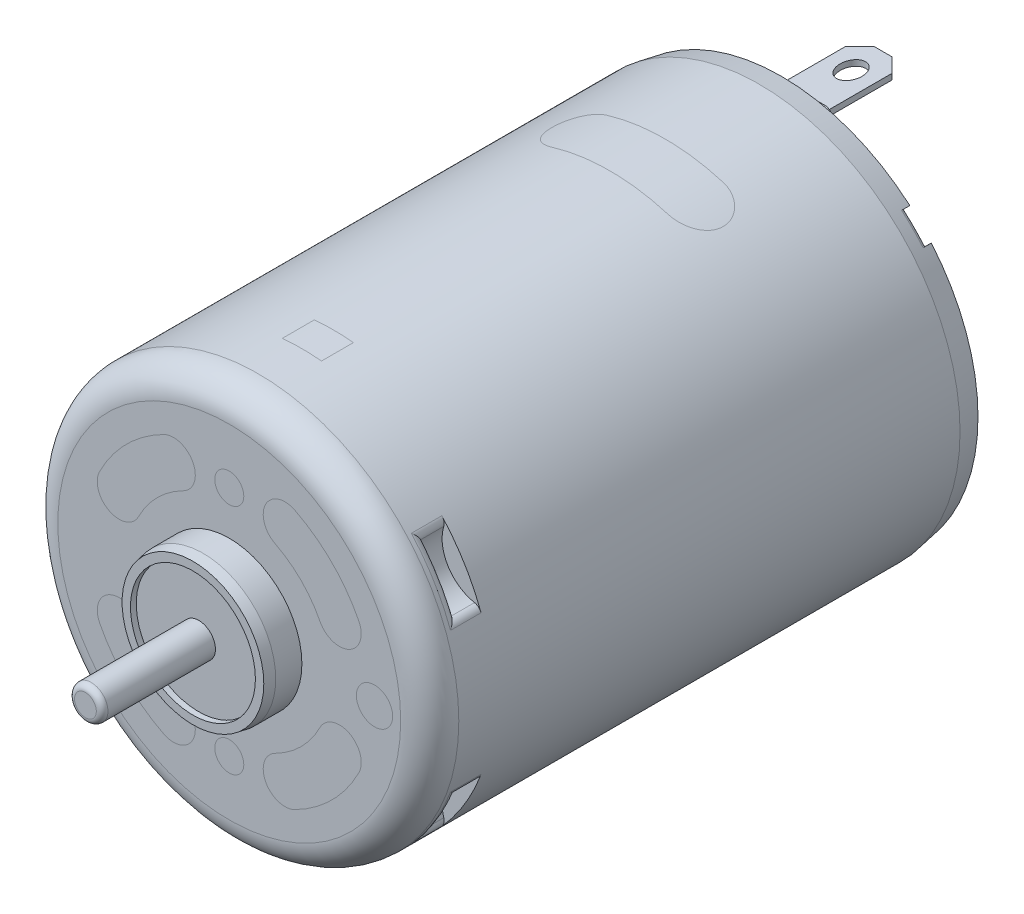
SolidWorks part; units mm, degrees
ref_plane "正面" through (0, 0, 0) normal (0, 0, 1) x (1, 0, 0)
ref_plane "平面" through (0, 0, 0) normal (0, 1, 0) x (1, 0, 0)
ref_plane "右側面" through (0, 0, 0) normal (1, 0, 0) x (0, 0, -1)
sketch "ｽｹｯﾁ1" plane through (0, 0, 0) normal (0, 0, 1) x (1, 0, 0)
  circle A0 centre (0, 0) radius 13.8
  dimension "D1" = 27.6
extrude "ﾎﾞｽ - 押し出し1" add sketch "ｽｹｯﾁ1" along normal blind 38
sketch "ｽｹｯﾁ2" plane through (0, 0, 0) normal (0, 0, -1) x (-1, 0, 0)
  circle A0 centre (0, 0) radius 9.6
  dimension "D1" = 19.2
extrude "ﾎﾞｽ - 押し出し2" add sketch "ｽｹｯﾁ2" along normal blind 0.3
sketch "ｽｹｯﾁ3" plane through (0, 0, 0) normal (0, 0, -1) x (-1, 0, 0)
  circle A0 centre (0, 0) radius 9.6 construction
  circle A1 centre (0, 0) radius 9.6
  circle A4 centre (0, 0) radius 13.2
  circle A5 centre (0, 0) radius 13.2
  dimension "D1" = 0.6
extrude "ｶｯﾄ - 押し出し1" cut sketch "ｽｹｯﾁ3" against normal blind 0.5
fillet "ﾌｨﾚｯﾄ1" radius 0.8 1 edges at (-9.6, 0, -0.3)
fillet "ﾌｨﾚｯﾄ2" radius 2 1 edges at (13.8, 0, 38)
sketch "ｽｹｯﾁ4" plane through (0, 0, 38) normal (0, 0, 1) x (1, 0, 0)
  circle A0 centre (0, 0) radius 5
  dimension "D1" = 10
extrude "ﾎﾞｽ - 押し出し3" add sketch "ｽｹｯﾁ4" along normal blind 2.5
sketch "ｽｹｯﾁ5" plane through (0, 0, 40.5) normal (0, 0, 1) x (1, 0, 0)
  circle A0 centre (0, 0) radius 1.15
  dimension "D1" = 2.3
extrude "ﾎﾞｽ - 押し出し4" add sketch "ｽｹｯﾁ5" along normal blind 7.4
fillet "ﾌｨﾚｯﾄ3" radius 0.4 1 edges at (1.15, 0, 47.9)
sketch "ｽｹｯﾁ6" plane through (0, 0, 40.5) normal (0, 0, 1) x (1, 0, 0)
  circle A0 centre (0, 0) radius 4.3
  circle A2 centre (0, 0) radius 1.15 construction
  circle A3 centre (0, 0) radius 1.15
  dimension "D1" = 8.6
extrude "ｶｯﾄ - 押し出し5" cut sketch "ｽｹｯﾁ6" against normal blind 0.4
chamfer "面取り1" distance 0.7 angle 10 1 edges at (5, 0, 40.5) first distance on face at (5, 0, 40.5)
chamfer "面取り2" distance 1.5 angle 10 1 edges at (13.8, 0, 0) first distance on face at (13.8, 0, 36)
sketch "ｽｹｯﾁ7" plane through (0, 0, -0.3) normal (0, 0, -1) x (-1, 0, 0)
  circle A0 centre (0, 0) radius 4.95
  dimension "D1" = 9.9
extrude "ﾎﾞｽ - 押し出し5" add sketch "ｽｹｯﾁ7" along normal blind 2.7
sketch "ｽｹｯﾁ8" plane through (0, 0, -3) normal (0, 0, -1) x (-1, 0, 0)
  circle A0 centre (0, 0) radius 1.15
  dimension "D1" = 2.3
extrude "ﾎﾞｽ - 押し出し6" add sketch "ｽｹｯﾁ8" along normal blind 0.2
sketch "ｽｹｯﾁ9" plane through (0, 0, -3) normal (0, 0, -1) x (-1, 0, 0)
  circle A1 centre (0, 0) radius 1.15 construction
  circle A2 centre (0, 0) radius 4.35
  circle A3 centre (0, 0) radius 4.35
  circle A4 centre (0, 0) radius 1.15
  dimension "D1" = 0.6
extrude "ｶｯﾄ - 押し出し6" cut sketch "ｽｹｯﾁ9" against normal blind 0.6
fillet "ﾌｨﾚｯﾄ4" radius 0.4 1 edges at (-1.15, 0, -3.2)
sketch "ｽｹｯﾁ10" plane through (0, 0, 38) normal (0, 0, 1) x (1, 0, 0)
  line L0 (-6.0104, 6.0104) -> (0, 0) construction
  line L1 (0, 0) -> (0, 8) construction
  circle A0 centre (0, 8) radius 1
  circle A1 centre (0, -8) radius 1
  circle A2 centre (0, 0) radius 0.75 construction
  arc A3 (-3.837, 7.5847) -> (-7.5847, 3.837) centre (0, 0) ccw construction
  arc A4 (-4.5141, 8.9232) -> (-8.9232, 4.5141) centre (0, 0) ccw
  arc A5 (-3.1599, 6.2462) -> (-6.2462, 3.1599) centre (0, 0) ccw
  arc A6 (-3.1599, 6.2462) -> (-4.5141, 8.9232) centre (-3.837, 7.5847) ccw
  arc A7 (-8.9232, 4.5141) -> (-6.2462, 3.1599) centre (-7.5847, 3.837) ccw
  circle A8 centre (0, 0) radius 5 construction
  arc A9 (7.5847, 3.837) -> (3.837, 7.5847) centre (0, 0) ccw construction
  arc A10 (8.9232, 4.5141) -> (4.5141, 8.9232) centre (0, 0) ccw
  arc A11 (6.2462, 3.1599) -> (3.1599, 6.2462) centre (0, 0) ccw
  arc A12 (6.2462, 3.1599) -> (8.9232, 4.5141) centre (7.5847, 3.837) ccw
  arc A13 (4.5141, 8.9232) -> (3.1599, 6.2462) centre (3.837, 7.5847) ccw
  arc A14 (3.837, -7.5847) -> (7.5847, -3.837) centre (0, 0) ccw construction
  arc A15 (4.5141, -8.9232) -> (8.9232, -4.5141) centre (0, 0) ccw
  arc A16 (3.1599, -6.2462) -> (6.2462, -3.1599) centre (0, 0) ccw
  arc A17 (3.1599, -6.2462) -> (4.5141, -8.9232) centre (3.837, -7.5847) ccw
  arc A18 (8.9232, -4.5141) -> (6.2462, -3.1599) centre (7.5847, -3.837) ccw
  arc A19 (-7.5847, -3.837) -> (-3.837, -7.5847) centre (0, 0) ccw construction
  arc A20 (-8.9232, -4.5141) -> (-4.5141, -8.9232) centre (0, 0) ccw
  arc A21 (-6.2462, -3.1599) -> (-3.1599, -6.2462) centre (0, 0) ccw
  arc A22 (-6.2462, -3.1599) -> (-8.9232, -4.5141) centre (-7.5847, -3.837) ccw
  arc A23 (-4.5141, -8.9232) -> (-3.1599, -6.2462) centre (-3.837, -7.5847) ccw
  circle A24 centre (10, 0) radius 1.25
  circle A25 centre (0, 0) radius 4.3 construction
  point P3 (-6.0104, 6.0104)
  point P6 (0, 0)
  point P24 (6.0104, 6.0104)
  point P31 (6.0104, -6.0104)
  point P38 (-6.0104, -6.0104)
  point P45 (0, 0)
  dimension "D2" = 2
  dimension "D3" = 8
  dimension "D4" = 1.5
  dimension "D6" = 2
  dimension "D9" = 10
  dimension "D10" = 2.5
  dimension "D5" = 5.3
  dimension "D7" = 45
  dimension "D1" = 2
  dimension "D8" = 4
split line "分割ﾗｲﾝ1"
ref_plane "平面1" through (0, 13.8, 0) normal (0, 1, 0) x (1, 0, 0)
sketch "ｽｹｯﾁ11" plane through (0, 13.8, 0) normal (0, 1, 0) x (1, 0, 0)
  line L0 (0, 0) -> (0, -38) construction
  line L2 (-4, -9.9) -> (4, -9.9) construction
  line L3 (-4, -8) -> (4, -8)
  line L4 (-4, -11.8) -> (4, -11.8)
  line L5 (13.5355, 0) -> (-13.5355, 0) construction
  line L6 (-5, -38) -> (5, -38) construction
  arc A0 (-4, -8) -> (-4, -11.8) centre (-4, -9.9) ccw
  arc A1 (4, -11.8) -> (4, -8) centre (4, -9.9) ccw
  point P7 (0, -9.9)
  point P12 (-5.9, -9.9)
  point P13 (5.9, -9.9)
  dimension "D1" = 11.8
  dimension "D2" = 3.8
  dimension "D3" = 8
split line "分割ﾗｲﾝ2"
sketch "ｽｹｯﾁ12" plane through (0, 0, 0) normal (0, 1, 0) x (1, 0, 0)
  line L0 (0, 0) -> (0, -38) construction
  line L1 (-5, -38) -> (5, -38) construction
  line L2 (-4, -11.8) -> (4, -11.8) construction
  line L3 (-1.35, -30.8) -> (1.35, -30.8)
  line L4 (-1.35, -30.8) -> (-1.35, -33)
  line L5 (-1.35, -33) -> (1.35, -33)
  line L6 (1.35, -30.8) -> (1.35, -33)
  line L7 (-1.35, -30.8) -> (1.35, -33) construction
  line L8 (-1.35, -33) -> (1.35, -30.8) construction
  point P5 (0, -31.9)
  dimension "D1" = 2.7
  dimension "D2" = 2.2
  dimension "D3" = 19
split line "分割ﾗｲﾝ3"
sketch "ｽｹｯﾁ13" plane through (0, 0, 0) normal (0, 1, 0) x (1, 0, 0)
  line L0 (0, 0) -> (0, -38) construction
  line L1 (-11.8, -38) -> (11.8, -38) construction
  line L2 (3, -26.5) -> (4.7, -26.5)
  line L3 (5.2, -26) -> (5.2, -21.076)
  line L4 (3, -16.5) -> (3.4319, -16.5)
  line L5 (2.5, -17) -> (2.5, -26)
  line L6 (4.5141, -38) -> (8.9232, -38) construction
  line L7 (3.9093, -16.8515) -> (5.1774, -20.9274)
  line L8 (-3.9093, -16.8515) -> (-5.1774, -20.9274)
  line L9 (-2.5, -17) -> (-2.5, -26)
  line L10 (-3, -16.5) -> (-3.4319, -16.5)
  line L11 (-5.2, -26) -> (-5.2, -21.076)
  line L12 (-3, -26.5) -> (-4.7, -26.5)
  arc A0 (3, -16.5) -> (2.5, -17) centre (3, -17) ccw
  arc A1 (3.4319, -16.5) -> (3.9093, -16.8515) centre (3.4319, -17) cw
  arc A2 (5.2, -21.076) -> (5.1774, -20.9274) centre (4.7, -21.076) ccw
  arc A3 (4.7, -26.5) -> (5.2, -26) centre (4.7, -26) ccw
  arc A4 (3, -26.5) -> (2.5, -26) centre (3, -26) cw
  arc A5 (-3, -26.5) -> (-2.5, -26) centre (-3, -26) ccw
  arc A6 (-4.7, -26.5) -> (-5.2, -26) centre (-4.7, -26) cw
  arc A7 (-5.2, -21.076) -> (-5.1774, -20.9274) centre (-4.7, -21.076) cw
  arc A8 (-3.4319, -16.5) -> (-3.9093, -16.8515) centre (-3.4319, -17) ccw
  arc A9 (-3, -16.5) -> (-2.5, -17) centre (-3, -17) cw
  point P14 (2.5, -16.5)
  point P17 (3.8, -16.5)
  point P20 (5.2, -21)
  point P23 (5.2, -26.5)
  point P26 (2.5, -26.5)
  point P42 (-2.5, -26.5)
  point P43 (-5.2, -26.5)
  point P44 (-5.2, -21)
  point P45 (-3.8, -16.5)
  point P46 (-2.5, -16.5)
  dimension "D7" = 0.5
  dimension "D1" = 10
  dimension "D2" = 2.7
  dimension "D3" = 5.5
  dimension "D4" = 2.5
  dimension "D5" = 11.5
  dimension "D6" = 1.3
split line "分割ﾗｲﾝ4"
sketch "ｽｹｯﾁ14" plane through (0, 0, 0.5) normal (0, 0, -1) x (-1, 0, 0)
  line L0 (2.5, -12.3) -> (2.5, -10.3)
  line L1 (-2.5, 12.3) -> (2.5, 12.3)
  line L2 (-2.5, 12.3) -> (-2.5, 10.3)
  line L3 (-2.5, 10.3) -> (2.5, 10.3)
  line L4 (2.5, 12.3) -> (2.5, 10.3)
  line L5 (-2.5, 12.3) -> (2.5, 10.3) construction
  line L6 (-2.5, 10.3) -> (2.5, 12.3) construction
  line L7 (2.5, -12.3) -> (-2.5, -12.3)
  line L8 (-2.5, -12.3) -> (-2.5, -10.3)
  line L9 (2.5, -10.3) -> (-2.5, -10.3)
  point P0 (0, 11.3)
  point P12 (0, 0)
  dimension "D1" = 2
  dimension "D2" = 5
  dimension "D4" = 24.6
  dimension "D3" = 2
extrude "ﾎﾞｽ - 押し出し7" add sketch "ｽｹｯﾁ14" along normal blind 1.5
fillet "ﾌｨﾚｯﾄ5" radius 0.5 8 edges at (2.5, -12.3, -0.25) (2.5, -10.3, -0.25) (-2.5, -12.3, -0.25) (-2.5, -10.3, -0.25) (2.5, 10.3, -0.25) (2.5, 12.3, -0.25) (-2.5, 10.3, -0.25) (-2.5, 12.3, -0.25)
sketch "ｽｹｯﾁ15" plane through (0, 0, -1) normal (0, 0, -1) x (-1, 0, 0)
  line L0 (2.5, 10.8) -> (2.5, 11.8) construction
  line L1 (-1.6, 11.5) -> (1.6, 11.5)
  line L2 (-1.6, 11.5) -> (-1.6, 11.1)
  line L3 (-1.6, 11.1) -> (1.6, 11.1)
  line L4 (1.6, 11.5) -> (1.6, 11.1)
  line L5 (-1.6, 11.5) -> (1.6, 11.1) construction
  line L6 (-1.6, 11.1) -> (1.6, 11.5) construction
  line L7 (2, 12.3) -> (-2, 12.3) construction
  line L8 (1.6, -11.5) -> (1.6, -11.1)
  line L9 (1.6, -11.5) -> (-1.6, -11.5)
  line L10 (-1.6, -11.5) -> (-1.6, -11.1)
  line L11 (1.6, -11.1) -> (-1.6, -11.1)
  point P0 (0, 11.3)
  point P7 (2.5, 11.3)
  point P10 (0, 12.3)
  point P17 (0, 0)
  dimension "D1" = 0.4
  dimension "D2" = 3.2
  dimension "D3" = 2
extrude "ﾎﾞｽ - 押し出し8" add sketch "ｽｹｯﾁ15" along normal blind 6
chamfer "面取り3" distance 1 angle 45 4 edges at (1.6, 11.3, -7) (-1.6, 11.3, -7) (1.6, -11.3, -7) (-1.6, -11.3, -7)
sketch "ｽｹｯﾁ16" plane through (0, 11.5, 0) normal (0, 1, 0) x (1, 0, 0)
  line L0 (-0.6, 7) -> (0.6, 7) construction
  ellipse E0 centre (0, 4.8) end of major axis (0, 5.8) minor radius 0.75
  dimension "D1" = 2
  dimension "D2" = 1.5
  dimension "D3" = 2.2
extrude "ｶｯﾄ - 押し出し8" cut sketch "ｽｹｯﾁ16" against normal through all
sketch "ｽｹｯﾁ18" plane through (0, 0, 0.5) normal (0, 0, -1) x (-1, 0, 0)
  line L0 (5.3033, 5.3033) -> (0, 0) construction
  line L1 (0, 0) -> (-6.2225, 6.2225) construction
  line L2 (-6.4952, 3.75) -> (0, 0) construction
  line L3 (0, 0) -> (-4.4, -7.621) construction
  line L4 (0, 0) -> (0, 13.8) construction
  arc A0 (3.2322, 6.7678) -> (6.7678, 3.2322) centre (0, 0) cw construction
  arc A1 (7.219, 3.4477) -> (3.4477, 7.219) centre (0, 0) ccw
  arc A2 (6.3166, 3.0168) -> (3.0168, 6.3166) centre (0, 0) ccw
  arc A3 (6.3166, 3.0168) -> (7.219, 3.4477) centre (6.7678, 3.2322) ccw
  arc A4 (3.4477, 7.219) -> (3.0168, 6.3166) centre (3.2322, 6.7678) ccw
  circle A5 centre (0, 0) radius 8.8 construction
  circle A6 centre (-6.4952, 3.75) radius 1
  circle A7 centre (0, 0) radius 13.8 construction
  circle A8 centre (6.4952, -3.75) radius 1
  arc A9 (-6.7678, -3.2322) -> (-3.2322, -6.7678) centre (0, 0) ccw construction
  arc A10 (-3.4477, -7.219) -> (-7.219, -3.4477) centre (0, 0) cw
  arc A11 (-3.0168, -6.3166) -> (-6.3166, -3.0168) centre (0, 0) cw
  arc A12 (-3.0168, -6.3166) -> (-3.4477, -7.219) centre (-3.2322, -6.7678) cw
  arc A13 (-7.219, -3.4477) -> (-6.3166, -3.0168) centre (-6.7678, -3.2322) cw
  point P4 (5.3033, 5.3033)
  point P25 (-5.3033, -5.3033)
  dimension "D1" = 0.5
  dimension "D3" = 2
  dimension "D2" = 5
  dimension "D4" = 7.5
  dimension "D5" = 7.5
  dimension "D6" = 45
  dimension "D7" = 60
split line "分割ﾗｲﾝ5"
sketch "ｽｹｯﾁ19" plane through (0, 0, 0.5) normal (0, 0, -1) x (-1, 0, 0)
  line L0 (-6.6697, -9.3683) -> (-3.9332, 10.8065) construction
  line L1 (-6.6697, -9.3683) -> (3.9332, -10.8065) construction
  line L2 (-3.9332, 10.8065) -> (6.6697, 9.3683) construction
  line L3 (3.9332, -10.8065) -> (6.6697, 9.3683) construction
  line L4 (-6.6697, -9.3683) -> (6.6697, 9.3683) construction
  line L5 (-3.9332, 10.8065) -> (3.9332, -10.8065) construction
  line L6 (0, 0) -> (0, 13.8) construction
  circle A0 centre (0, 0) radius 13.8 construction
  circle A2 centre (-3.9332, 10.8065) radius 1.2
  circle A3 centre (6.6697, 9.3683) radius 1.2
  circle A4 centre (3.9332, -10.8065) radius 1.2
  circle A5 centre (-6.6697, -9.3683) radius 1.2
  point P1 (0, 0)
  dimension "D4" = 2.4
  dimension "D1" = 20
  dimension "D2" = 23
  dimension "D3" = 10.7
extrude "ﾎﾞｽ - 押し出し9" add sketch "ｽｹｯﾁ19" along normal blind 0.7
chamfer "面取り4" distance 0.5 angle 45 4 edges at (5.4697, -9.3683, -0.2) (-5.1332, -10.8065, -0.2) (-7.8697, 9.3683, -0.2) (2.7332, 10.8065, -0.2)
chamfer "面取り5" distance 0.6 angle 10 1 edges at (-4.95, 0, -3) first distance on face at (-4.95, 0, -3)
ref_plane "平面2" through (0, 0, 35.1) normal (0, 0, 1) x (1, 0, 0)
sketch "ｽｹｯﾁ20" plane through (0, 0, 35.1) normal (0, 0, 1) x (1, 0, 0)
  line L1 (-13, -7.9) -> (13, -7.9) construction
  line L2 (-13, -7.9) -> (-13, 7.9) construction
  line L3 (-13, 7.9) -> (13, 7.9) construction
  line L4 (13, -7.9) -> (13, 7.9) construction
  line L5 (-13, -7.9) -> (13, 7.9) construction
  line L6 (-13, 7.9) -> (13, -7.9) construction
  circle A0 centre (-13, 7.9) radius 2.75
  circle A1 centre (13, 7.9) radius 2.75
  circle A2 centre (13, -7.9) radius 2.75
  circle A3 centre (-13, -7.9) radius 2.75
  point P0 (0, 0)
  dimension "D1" = 5.5
  dimension "D2" = 15.8
  dimension "D3" = 26
extrude "ｶｯﾄ - 押し出し9" cut sketch "ｽｹｯﾁ20" against normal blind 1.5
fillet "ﾌｨﾚｯﾄ6" radius 0.6 12 edges at (-10.4735, 8.9859, 34.35) (-11.7932, 7.1666, 35.1) (-12.8001, 5.1573, 34.35) (-12.8001, -5.1573, 34.35) (-11.7932, -7.1666, 35.1) (-10.4735, -8.9859, 34.35) (10.4735, -8.9859, 34.35) (11.7932, -7.1666, 35.1) (12.8001, -5.1573, 34.35) (12.8001, 5.1573, 34.35) (11.7932, 7.1666, 35.1) (10.4735, 8.9859, 34.35)
sketch "ｽｹｯﾁ21" plane through (0, 0, 0) normal (0, 0, -1) x (-1, 0, 0)
  line L0 (9.1406, 10.5413) -> (8.6047, 10.0099)
  line L1 (-9.612, -9.53) -> (9.612, -9.53) construction
  line L2 (-9.612, -9.53) -> (-9.612, 9.53) construction
  line L3 (-9.612, 9.53) -> (9.612, 9.53) construction
  line L4 (9.612, -9.53) -> (9.612, 9.53) construction
  line L5 (-9.612, -9.53) -> (9.612, 9.53) construction
  line L6 (-9.612, 9.53) -> (9.612, -9.53) construction
  line L7 (9.1406, 10.5413) -> (10.6192, 9.05)
  line L8 (8.6047, 10.0099) -> (10.0833, 8.5187)
  line L9 (10.6192, 9.05) -> (10.0833, 8.5187)
  line L10 (9.1406, 10.5413) -> (10.0833, 8.5187) construction
  line L11 (8.6047, 10.0099) -> (10.6192, 9.05) construction
  line L12 (-10.6192, 9.05) -> (-10.0833, 8.5187)
  line L13 (-10.6192, 9.05) -> (-9.1406, 10.5413)
  line L14 (-10.0833, 8.5187) -> (-8.6047, 10.0099)
  line L15 (-9.1406, 10.5413) -> (-8.6047, 10.0099)
  line L16 (-10.6192, 9.05) -> (-8.6047, 10.0099) construction
  line L17 (-10.0833, 8.5187) -> (-9.1406, 10.5413) construction
  line L18 (9.1406, -10.5413) -> (8.6047, -10.0099)
  line L19 (9.1406, -10.5413) -> (10.6192, -9.05)
  line L20 (8.6047, -10.0099) -> (10.0833, -8.5187)
  line L21 (10.6192, -9.05) -> (10.0833, -8.5187)
  line L22 (9.1406, -10.5413) -> (10.0833, -8.5187) construction
  line L23 (8.6047, -10.0099) -> (10.6192, -9.05) construction
  line L24 (-9.1406, -10.5413) -> (-8.6047, -10.0099)
  line L25 (-9.1406, -10.5413) -> (-10.6192, -9.05)
  line L26 (-8.6047, -10.0099) -> (-10.0833, -8.5187)
  line L27 (-10.6192, -9.05) -> (-10.0833, -8.5187)
  line L28 (-9.1406, -10.5413) -> (-10.0833, -8.5187) construction
  line L29 (-8.6047, -10.0099) -> (-10.6192, -9.05) construction
  circle A0 centre (0, 0) radius 13.5355 construction
  circle A1 centre (0, 0) radius 13.2 construction
  point P0 (0, 0)
  point P8 (9.344, 9.2643)
  point P9 (-9.344, 9.2643)
  point P10 (-9.344, -9.2643)
  point P15 (9.344, -9.2643)
  dimension "D1" = 2.1
  dimension "D2" = 18.1
extrude "ｶｯﾄ - 押し出し10" cut sketch "ｽｹｯﾁ21" against normal blind 0.4
fillet "ﾌｨﾚｯﾄ7" radius 0.3 4 edges at (-9.662, 9.5796, 0.4) (-9.662, -9.5796, 0.4) (9.662, -9.5796, 0.4) (9.662, 9.5796, 0.4)
